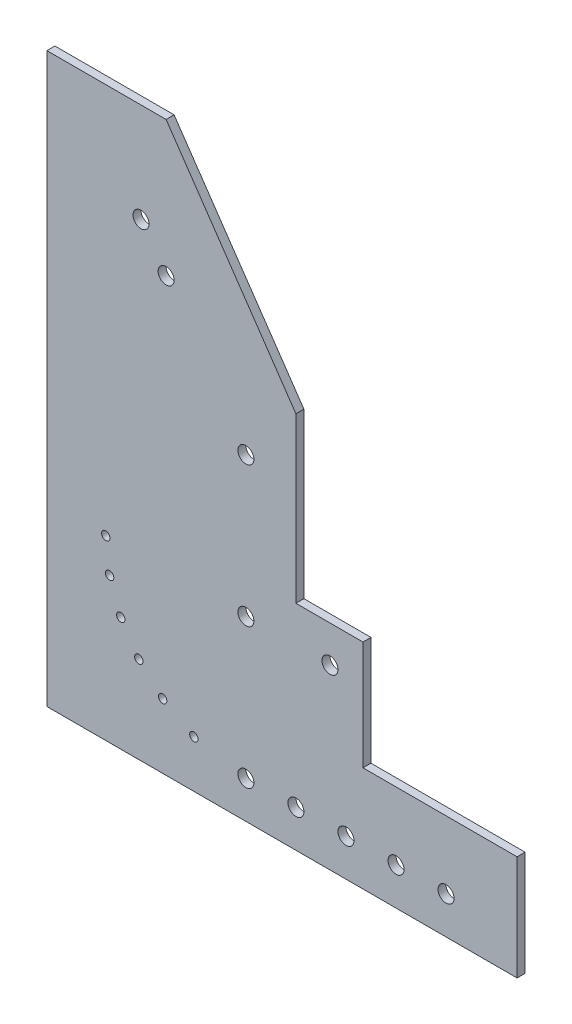
SolidWorks part; units mm, degrees
note: The reader was unsure of these and kept them because the rebuilt part matched: shared geometry of "草图2<4>".
ref_plane "前视基准面" through (0, 0, 0) normal (0, 0, 1) x (1, 0, 0)
ref_plane "上视基准面" through (0, 0, 0) normal (0, 1, 0) x (1, 0, 0)
ref_plane "右视基准面" through (0, 0, 0) normal (1, 0, 0) x (0, 0, -1)
other "Configuration Table"
sketch "草图2" plane through (0, 0, 0) normal (0, 0, 1) x (1, 0, 0)
  line L0 (0, 0) -> (150, 0)
  line L1 (0, 0) -> (0, 49.8489)
  line L2 (80, 0) -> (80, -33.3297)
  line L3 (0, 0) -> (-51.4118, 0)
  line L4 (80, 0) -> (80, -47.5879)
  line L5 (-22, 65) -> (0, 65)
  line L6 (48, 65) -> (0, 0)
  line L7 (-22, 65) -> (-14.4932, 33.4628)
  line L8 (48, 65) -> (-27.831, 46.9501)
  line L9 (-14.4932, 33.4628) -> (6.417, 8.6897)
  line L10 (48, 65) -> (-15.8078, 11.1418)
  line L11 (48, -5) -> (148, -5)
  line L12 (-22, 65) -> (-22, 135)
  line L13 (48, 65) -> (48, 135)
  line L14 (48, 135) -> (-12.8196, 222.7778)
  line L15 (48, 65) -> (198.0979, 65)
  line L16 (-51.4118, -23.646) -> (-51.4118, 260.1542)
  line L17 (-51.4118, 260.1542) -> (8.133, 260.1542)
  line L18 (8.133, 260.1542) -> (73, 165.2222)
  line L19 (73, 165.2222) -> (73, 83.2355)
  line L20 (73, 83.2355) -> (106.4852, 83.2355)
  line L21 (106.4852, 83.2355) -> (106.4852, 28.799)
  line L22 (106.4852, 28.799) -> (183.493, 28.799)
  line L23 (183.493, 28.799) -> (183.493, -23.646)
  line L24 (183.493, -23.646) -> (-51.4118, -23.646)
  circle A0 centre (48, 65) radius 4
  circle A3 centre (6.417, 8.6897) radius 2.1
  circle A4 centre (-22, 65) radius 2.1
  arc A5 (-22, 65) -> (6.417, 8.6897) centre (48, 65) ccw
  arc A6 (6.417, 8.6897) -> (22.0192, 0) centre (48, 65) ccw
  circle A7 centre (-14.4932, 33.4628) radius 2.1
  circle A8 centre (22.0192, 0) radius 2.1
  circle A9 centre (-20.0975, 48.7909) radius 2.1
  circle A10 centre (-5.492, 19.8491) radius 2.1
  arc A11 (-22, 65) -> (48, -5) centre (48, 65) ccw
  circle A12 centre (48, -5) radius 4
  circle A13 centre (148, -5) radius 4
  circle A14 centre (98, -5) radius 4
  circle A15 centre (73, -5) radius 4
  circle A16 centre (123, -5) radius 4
  circle A17 centre (48, 135) radius 4
  arc A18 (-22, 135) -> (8.133, 192.538) centre (48, 135) cw
  circle A19 centre (8.133, 192.538) radius 4
  circle A20 centre (-4.3966, 210.6214) radius 4
  circle A21 centre (90, 65) radius 4
  point P13 (6.417, 8.6897)
  point P32 (73, -5)
  point P33 (98, -5)
  point P34 (48, -5)
  point P36 (123, -5)
  dimension "D3" = 65
  dimension "D7" = 25
  dimension "D10" = 70
  dimension "D11" = 22
  dimension "D12" = 60
  dimension "D13" = 8
  dimension "D14" = 8
  dimension "D15" = 8
  dimension "D16" = 8
  dimension "D17" = 8
  dimension "D18" = 8
  dimension "D19" = 8
  dimension "D20" = 8
  dimension "D21" = 8
  dimension "D22" = 8
  dimension "D1" = 80
  dimension "D2" = 150
  dimension "D4" = 70
  dimension "D5" = 48
  dimension "D6" = 22
  dimension "D8" = 25
  dimension "D9" = 25
extrude "凸台-拉伸2" add sketch "草图2" along normal blind 4
extrude "切除-拉伸1" cut sketch "草图2<4>" against normal mid plane 30 contours A12 | A15 | A14 | A16 | A13 | A8 | A3 | A10 | A7 | A9 | A4
sketch "草图2<4>" plane through (0, 0, 0) normal (0, 0, 1) x (1, 0, 0) same geometry as "草图2"
